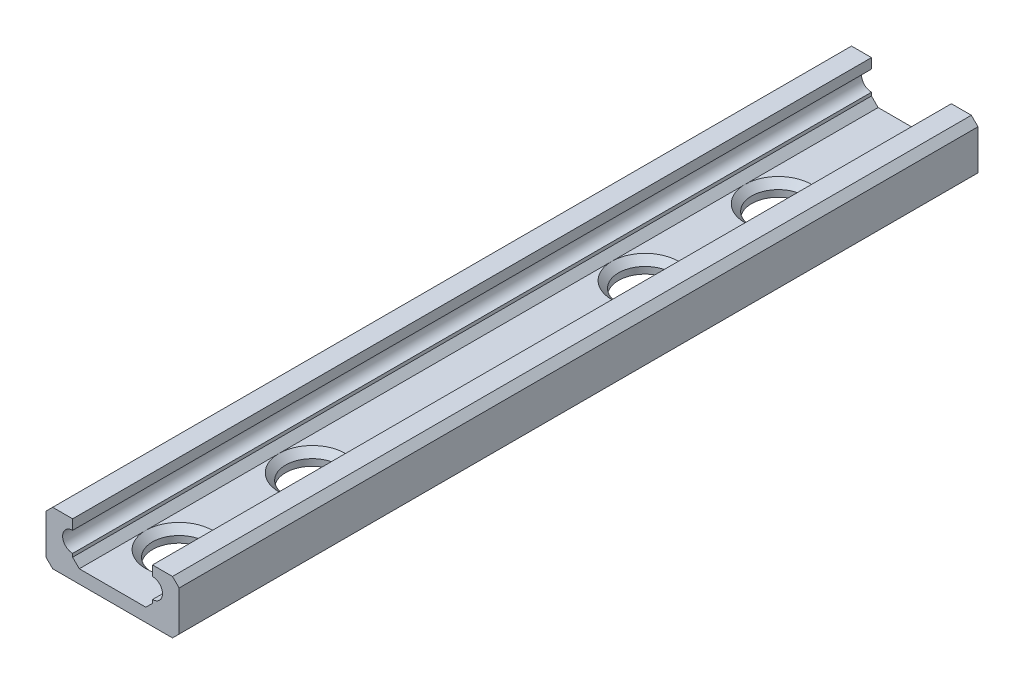
SolidWorks part; units mm, degrees
material "Nickel"
ref_plane "Front Plane" through (0, 0, 0) normal (0, 0, 1) x (1, 0, 0)
ref_plane "Top Plane" through (0, 0, 0) normal (0, 1, 0) x (1, 0, 0)
ref_plane "Right Plane" through (0, 0, 0) normal (1, 0, 0) x (0, 0, -1)
sketch "Sketch1" plane through (0, 0, 0) normal (0, 0, 1) x (1, 0, 0)
  line L0 (0, 0.5) -> (0, 0) construction
  line L1 (-5, 2) -> (5, 2)
  line L2 (-5, 2) -> (-5, -2)
  line L3 (-5, -2) -> (5, -2)
  line L4 (5, 2) -> (5, -2)
  line L5 (-5, 2) -> (5, -2) construction
  line L6 (-5, -2) -> (5, 2) construction
  line L7 (3, -1) -> (-3, -1)
  line L8 (3, -1) -> (3, 2)
  line L9 (3, 2) -> (-3, 2)
  line L10 (-3, -1) -> (-3, 2)
  line L11 (3, -1) -> (-3, 2) construction
  line L12 (3, 2) -> (-3, -1) construction
  circle A0 centre (3, 0.5) radius 0.75
  circle A1 centre (-3, 0.5) radius 0.75
  point P0 (0, 0.5)
  dimension "D5" = 1.5
  dimension "D6" = 1.5
  dimension "D1" = 4
  dimension "D2" = 2
  dimension "D3" = 1
  dimension "D4" = 10
extrude "Boss-Extrude1" add sketch "Sketch1" along normal blind 100 contours A1 L10 L1 L2 L3 L4 L8 A0 L7 region at (-4, 1.8923, 0)
chamfer "Chamfer1" distance 0.5 angle 45 6 edges at (3, -1, 50) (-3, -1, 50) (5, -2, 50) (5, 2, 50) (-5, -2, 50) (-5, 2, 50)
sketch "Sketch2" plane through (0, -1, 0) normal (0, 1, 0) x (1, 0, 0)
  line L0 (0, 0) -> (0, -10) construction
  line L1 (2.5, 0) -> (-2.5, 0) construction
  dimension "D1" = 10
sketch "Sketch5" plane through (0, -1, 0) normal (0, 1, 0) x (1, 0, 0)
  line L0 (0, -10) -> (0, -20) construction
  circle A0 centre (0, -10) radius 2
  circle A1 centre (0, -20) radius 2
  dimension "D1" = 4
  dimension "D2" = 4
  dimension "D3" = 10
extrude "Cut-Extrude1" cut sketch "Sketch5" against normal blind 200
chamfer "Chamfer2" distance 0.5 angle 45 2 edges at (0, -1, 12) (0, -1, 22)
pattern_linear "LPattern1" count 3 spacing 35 along (0, 0, 1) of "Cut-Extrude1", "Chamfer2"
sketch "Sketch6" plane through (0, 0, 0) normal (0, 1, 0) x (1, 0, 0)
  line L0 (0, 0) -> (0, -60) construction
  line L1 (7.5, -100) -> (-7.5, -100)
  line L2 (7.5, -100) -> (7.5, -60)
  line L3 (7.5, -60) -> (-7.5, -60)
  line L4 (-7.5, -100) -> (-7.5, -60)
  line L5 (2.5, 0) -> (-2.5, 0) construction
  dimension "D1" = 60
  dimension "D2" = 15
  dimension "D3" = 40
extrude "Cut-Extrude2" cut sketch "Sketch6" against normal blind 10 and the other way blind 10
